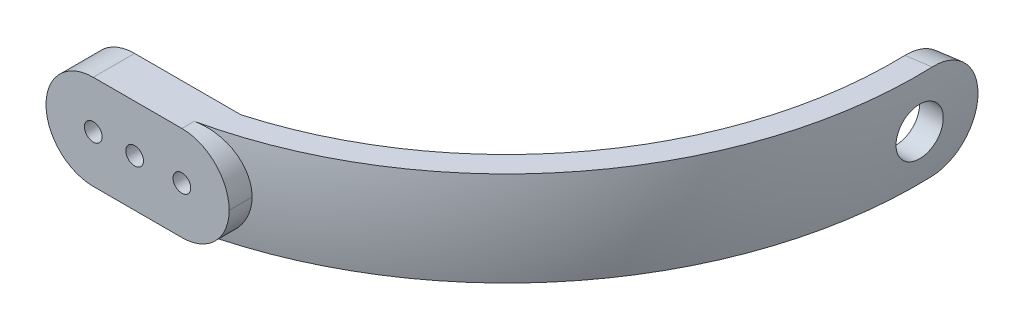
SolidWorks part; units mm, degrees
ref_plane "前视基准面" through (0, 0, 0) normal (0, 0, 1) x (1, 0, 0)
ref_plane "上视基准面" through (0, 0, 0) normal (0, 1, 0) x (1, 0, 0)
ref_plane "右视基准面" through (0, 0, 0) normal (1, 0, 0) x (0, 0, -1)
sketch "草图2" plane through (0, 0, 0) normal (0, 0, 1) x (1, 0, 0)
  line L0 (0, 0) -> (70, 0) construction
  line L1 (65.5134, 8) -> (69.5414, 8)
  line L2 (0, 0) -> (0, 18.8305) construction
  line L3 (69.5414, -8) -> (65.5134, -8)
  arc A0 (65.5134, -8) -> (65.5134, 8) centre (0, 0) ccw
  arc A1 (69.5414, -8) -> (69.5414, 8) centre (0, 0) ccw
  dimension "D1" = 8
  dimension "D3" = 66
  dimension "D4" = 70
  dimension "D2" = 8
revolve "旋转1" add sketch "草图2" angle 98.681 about L2
sketch "草图4" plane through (0, 0, 0) normal (1, 0, 0) x (0, 0, -1)
  circle A0 centre (0, 0) radius 4
extrude "切除-拉伸2" cut sketch "草图4" along normal through all
sketch "草图6" plane through (0, 0, 0) normal (0, 0, 1) x (1, 0, 0)
  line L1 (-18, -11) -> (18, -11)
  line L2 (-18, -11) -> (-18, 11)
  line L3 (-18, 11) -> (18, 11)
  line L4 (18, -11) -> (18, 11)
  line L5 (-18, -11) -> (18, 11) construction
  line L6 (-18, 11) -> (18, -11) construction
  point P0 (0, 0)
  dimension "D1" = 36
  dimension "D2" = 22
extrude "切除-拉伸3" cut sketch "草图6" along normal through all
ref_plane "基准面1" through (0, 0, 70) normal (0, 0, 1) x (1, 0, 0)
sketch "草图7" plane through (0, 0, 70) normal (0, 0, 1) x (1, 0, 0)
  line L0 (0, 0) -> (29.872, 0) construction
  line L1 (-8, -8) -> (23, -8)
  line L2 (-8, -8) -> (-8, 8)
  line L3 (-8, 8) -> (23, 8)
  line L4 (23, -8) -> (23, 8)
  circle A0 centre (0, 0) radius 1.5
  circle A1 centre (7, 0) radius 1.5
  circle A2 centre (15, 0) radius 1.5
  point P7 (7.5, -8)
  dimension "D5" = 3
  dimension "D6" = 3
  dimension "D7" = 3
  dimension "D1" = 16
  dimension "D2" = 8
  dimension "D3" = 23
  dimension "D4" = 8
  dimension "D8" = 7
  dimension "D9" = 15
extrude "凸台-拉伸1" add sketch "草图7" against normal blind 7
fillet "圆角1" radius 8 6 edges at (66.7537, -8, -10.1923) (66.7537, 8, -10.1923) (23, -8, 67.8139) (23, 8, 67.8139) (-8, -8, 66.5) (-8, 8, 66.5)
